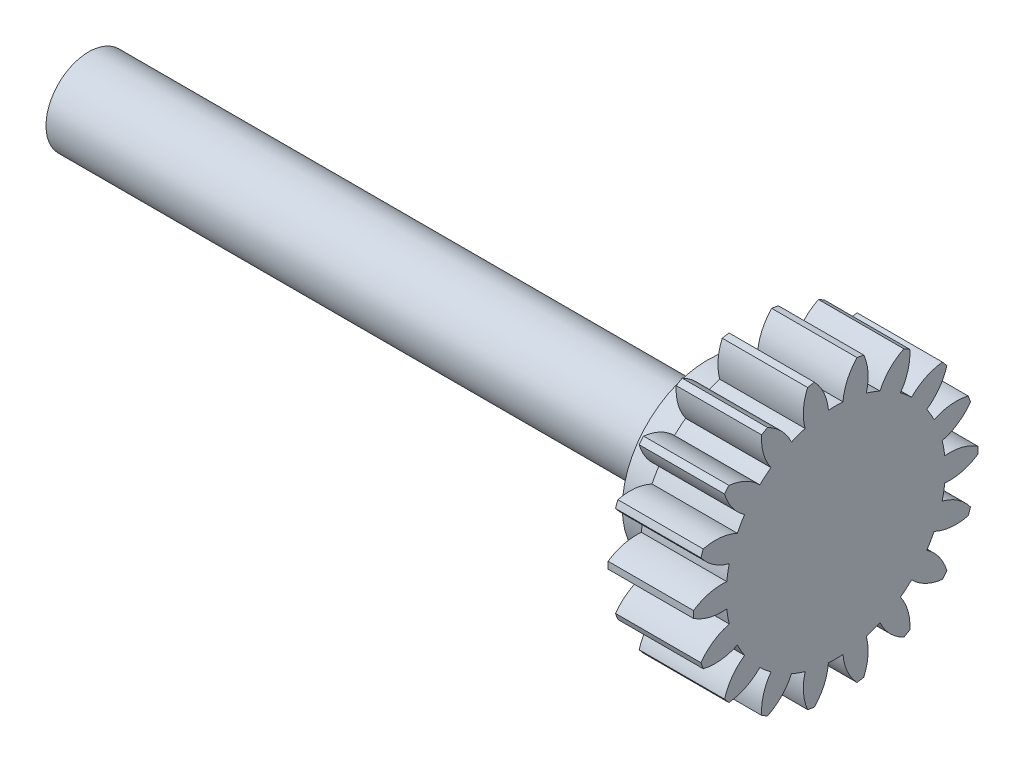
SolidWorks part; units mm, degrees
material "PET"
ref_plane "Plane1" through (0, 0, 0) normal (0, 0, 1) x (1, 0, 0)
ref_plane "Plane2" through (0, 0, 0) normal (0, 1, 0) x (1, 0, 0)
ref_plane "Plane3" through (0, 0, 0) normal (1, 0, 0) x (0, 0, -1)
sketch "HoldingSke" plane through (0, 0, 0) normal (0, 1, 0) x (1, 0, 0)
  line L0 (0, 0) -> (1159.5281, -376.7535)
  line L1 (-15, 0) -> (100, 0) construction
  line L2 (0, 0) -> (-2.1039, 2.3779)
  line L3 (0, 0) -> (-11.863, 4.5341)
  line L4 (0, 0) -> (8.2133, 2.6687)
  line L5 (0, 0) -> (-47.5972, -17.7524)
  line L6 (0, 0) -> (-2.632, -1.7758)
  line L7 (-2.1039, 2.3779) -> (8.8308, 51.9873)
  line L8 (-76.2, 54.61) -> (-75.184, 54.61)
  line L9 (-71.009, 38.7566) -> (-53.1078, 45.2721)
  line L10 (-76.2, 71.12) -> (104.1128, 71.12)
  line L11 (0, 0) -> (-3.175, 0)
  line L12 (-76.2, 101.6) -> (-76.1787, 101.6)
  line L13 (24.9733, 27.94) -> (52.9518, 28.4284)
  line L14 (24.9733, 27.94) -> (25.0241, 27.9398)
  line L15 (24.9733, 27.94) -> (100.4021, 29.52)
  circle A0 centre (0, 0) radius 0.3969
  circle A1 centre (0, 0) radius 4.0767
  circle A2 centre (0, 0) radius 38.1
  circle A3 centre (0, 0) radius 0.3969
  dimension "MHD" = 8.1534
  dimension "Hub_dia" = 76.2
  dimension "Bore" = 0.7937
  dimension "MBD" = 0.7937
  dimension "Num_teeth" = 18
  dimension "Pitch" = 1219.2
  dimension "Overall_len" = 50.8
  dimension "Show_teeth" = 18
  dimension "Thickness" = 3.175
  dimension "OAL" = 50.8002
  dimension "T_dim" = 1.016
  dimension "Ap" = 20
  dimension "H" = 19.05
  dimension "Pitch_radius" = 180.3128
  dimension "Width" = 3.175
  dimension "Backlash" = 0.0213
  dimension "Addendum_fac" = 1
  dimension "Dedendum_fac" = 1.2
  dimension "Clearance_fac" = 0.2
  dimension "Dedendum_add" = 0.0508
sketch "BasProSke" plane through (0, 0, 0) normal (0, 1, 0) x (1, 0, 0)
  line L0 (-10, 0) -> (60, 0) construction
  line L1 (0, 0) -> (0, 5.2917)
  line L2 (0, 0) -> (3.175, 0)
  line L3 (3.175, 0) -> (3.175, 5.2917)
  line L4 (3.175, 5.2917) -> (0, 5.2917)
  dimension "Thickness" = 3.175
  dimension "Diameter" = 10.5833
revolve "Base-Revolve" add sketch "BasProSke" angle 360 about L0
sketch "TooCutSke" plane through (0, 0, 0) normal (1, 0, 0) x (0, 0, -1)
  line L1 (0, 0) -> (0, 107) construction
  line L2 (0, 0) -> (-0.4524, 4.741) construction
  line L3 (0, 0) -> (-1.6488, 9.3507) construction
  line L4 (-0.4524, 4.741) -> (-0.8244, 4.6754) construction
  arc A0 (0.27, 4.0677) -> (-0.27, 4.0677) centre (0, 0) ccw
  arc A1 (0.8145, 5.2543) -> (-0.8145, 5.2543) centre (0, 0) ccw
  circle A2 centre (0, 0) radius 4.7625 construction
  circle A3 centre (0, 0) radius 4.4753 construction
  arc A4 (-0.27, 4.0677) -> (-0.8145, 5.2543) centre (-2.1688, 3.9146) ccw
  arc A5 (0.8145, 5.2543) -> (0.27, 4.0677) centre (2.1688, 3.9146) ccw
  dimension "Root_dia" = 8.1534
  dimension "Overcut_dia" = 10.6341
  dimension "Pitch_dia" = 9.525
  dimension "Base_dia" = 8.9506
  dimension "Flank_rad" = 1.905
  dimension "Half_ang" = 10
  dimension "Half_CT" = 0.3777
extrude "ToothCut" cut sketch "TooCutSke" along normal through all
fillet "Breaks" [suppressed] radius 0.0106 tangent propagation no
fillet "RootFillets" [suppressed] radius 0.1566
pattern_circular "TeethCuts" count 18 every 20 about axis through (-10, 0, 0) along (1, 0, 0) of "ToothCut", "RootFillets", "Breaks"
sketch "HubNeaOneSke" plane through (0, 0, 0) normal (-1, 0, 0) x (0, 0, 1)
  circle A0 centre (0, 0) radius 4.0767
  dimension "Diameter" = 8.1534
extrude "HubNearOne" [suppressed] add sketch "HubNeaOneSke" along normal blind 47.6252
sketch "HubNeaBotSke" plane through (0, 0, 0) normal (-1, 0, 0) x (0, 0, 1)
  circle A0 centre (0, 0) radius 4.0767
  dimension "Diameter" = 8.1534
extrude "HubNearBoth" [suppressed] add sketch "HubNeaBotSke" along normal blind 23.8126
ref_plane "FarPln" through (3.175, 0, 0) normal (1, 0, 0) x (0, 0, -1)
sketch "HubFarSke" plane through (3.175, 0, 0) normal (1, 0, 0) x (0, 0, -1)
  circle A0 centre (0, 0) radius 4.0767
  dimension "Diameter" = 8.1534
extrude "HubFar" [suppressed] add sketch "HubFarSke" along normal blind 23.8126
sketch "BorSke" plane through (0, 0, 0) normal (1, 0, 0) x (0, 0, -1)
  circle A0 centre (0, 0) radius 0.3969
  dimension "Diameter" = 0.7937
extrude "Bore" [suppressed] cut sketch "BorSke" along normal mid plane 101.6004
sketch "KeySke" plane through (0, 0, 0) normal (1, 0, 0) x (0, 0, -1)
  line L0 (-0.127, 0) -> (-0.127, 0.6191)
  line L1 (-0.127, 0.6191) -> (0.127, 0.6191)
  line L2 (0.127, 0.6191) -> (0.127, 0)
  line L3 (0, 0) -> (0, 34) construction
  line L4 (-0.127, 0) -> (0.127, 0)
  dimension "Offset" = 0.6191
  dimension "Width" = 0.254
extrude "Keyway" [suppressed] cut sketch "KeySke" along normal mid plane 101.6004
pattern_circular "Keyway2" [suppressed] count 2 every 90 about axis through (-10, 0, 0) along (1, 0, 0) reverse direction yes
sketch "Sketch1" [suppressed] plane through (0, 0, 0) normal (-1, 0, 0) x (0, 0, 1)
  circle A0 centre (0, 0) radius 2.7781
  dimension "D1" = 5.5562
extrude "Cut-Extrude2" [suppressed] cut sketch "Sketch1" against normal offset from surface (1.5875 mm away) 1.5875 up to face at (3.175, 0, 0)
sketch "Sketch2" plane through (0, 0, 0) normal (-1, 0, 0) x (0, 0, 1)
  circle A0 centre (0, 0) radius 1.5875
  dimension "D1" = 3.175
extrude "Cut-Extrude3" [suppressed] cut sketch "Sketch2" against normal through all contours A0
extrude "Boss-Extrude1" add sketch "Sketch2<3>" along normal blind 24.6062
sketch "Sketch2<3>" plane through (0, 0, 0) normal (-1, 0, 0) x (0, 0, 1) same geometry as "Sketch2"
sketch "Sketch3" plane through (0, 0, 0) normal (-1, 0, 0) x (0, 0, 1)
  circle A0 centre (0, 0) radius 3.175
  dimension "D1" = 6.35
extrude "Boss-Extrude2" add sketch "Sketch3" along normal blind 1.5875
ref_plane "Plane4" through (1.5875, 0, 0) normal (1, 0, 0) x (0, 0, -1)
sketch "Sketch4" plane through (1.5875, 0, 0) normal (1, 0, 0) x (0, 0, -1)
  circle A0 centre (0, 0) radius 4.7625
  dimension "D1" = 9.525
equation "' \"Pitch@HoldingSke\" = 4"
equation "'\"Num_teeth@HoldingSke\" = 18"
equation "' \"Ap@HoldingSke\" =  20"
equation "' \"Ap@HoldingSke\" = 20"
equation "' \"Width@HoldingSke\" = 0.5"
equation "' \"Hub_dia@HoldingSke\"= 1"
equation "' \"Hub_dia@HoldingSke\" = 1"
equation "' \"Overall_len@HoldingSke\" = 1.0"
equation "' \"Bore@HoldingSke\" = 0.75"
equation "' \"T_dim@HoldingSke\" = 0.85"
equation "' \"Width@KeySke\" = 0.25"
equation "' \"Show_teeth@HoldingSke\" = 13"
equation "' \"Backlash@HoldingSke\" = 0.009"
equation "' \"Addendum_fac@HoldingSke\" = 1.0"
equation "' \"Dedendum_fac@HoldingSke\" = 1.25"
equation "' \"Dedendum_add@HoldingSke\" = 0.00005"
equation "' \"Clearance_fac@HoldingSke\" = 0.25"
equation "' \"Pitch@HoldingSke\" = 0.5"
equation "' \"Num_teeth@HoldingSke\" = 23"
equation "' \"Show_teeth@HoldingSke\" = 23"
equation "' \"Backlash@HoldingSke\" = 0.0375"
equation "\"Overcut_dia@TooCutSke\" = (\"Num_teeth@HoldingSke\" + 2 * \"Addendum_fac@HoldingSke\") / \"Pitch@HoldingSke\" + 0.002"
equation "\"Pitch_dia@TooCutSke\" = \"Num_teeth@HoldingSke\" / \"Pitch@HoldingSke\""
equation "\"Base_dia@TooCutSke\" = \"Num_teeth@HoldingSke\" / \"Pitch@HoldingSke\" * cos((\"Ap@HoldingSke\"  * 3.14159265 / 180))"
equation "\"Root_dia@TooCutSke\" = (\"Num_teeth@HoldingSke\" + 2) / \"Pitch@HoldingSke\" - 2 * (\"Addendum_fac@HoldingSke\" + \"Dedendum_fac@HoldingSke\") / \"Pitch@HoldingSke\" - \"Dedendum_add@HoldingSke\" * 2"
equation "\"Half_ang@TooCutSke\" = 180 / \"Num_teeth@HoldingSke\""
equation "\"Half_CT@TooCutSke\" = \"Num_teeth@HoldingSke\" / \"Pitch@HoldingSke\" * sin((3.14159265 / 2 / \"Num_teeth@HoldingSke\")) / 2 - 7 * \"Backlash@HoldingSke\" / 4"
equation "\"Flank_rad@TooCutSke\" = \"Num_teeth@HoldingSke\" / \"Pitch@HoldingSke\" / 5"
equation "\"Radius@RootFillets\" = \"Clearance_fac@HoldingSke\" / \"Pitch@HoldingSke\" + \"Dedendum_add@HoldingSke\""
equation "\"Break_rad@Breaks\" = 0.02 / \"Pitch@HoldingSke\""
equation "\"Thickness@HoldingSke\" = \"Width@HoldingSke\""
equation "\"OAL@HoldingSke\" = \"Thickness@HoldingSke\""
equation "\"MHD@HoldingSke\" = (\"Num_teeth@HoldingSke\" + 2) / \"Pitch@HoldingSke\" - 2 * (\"Addendum_fac@HoldingSke\" + \"Dedendum_fac@HoldingSke\")  / \"Pitch@HoldingSke\" - \"Dedendum_add@HoldingSke\" * 2"
equation "\"MBD@HoldingSke\" = (\"Num_teeth@HoldingSke\" + 2) / \"Pitch@HoldingSke\" - 2 * (\"Addendum_fac@HoldingSke\" + \"Dedendum_fac@HoldingSke\")  / \"Pitch@HoldingSke\" - \"Dedendum_add@HoldingSke\" * 2 - 0.002"
equation "\"MHD@HoldingSke\" = ((sgn( \"MHD@HoldingSke\" - \"Hub_dia@HoldingSke\" )-1)*( \"MHD@HoldingSke\" - \"Hub_dia@HoldingSke\" ))/-2+ \"Hub_dia@HoldingSke\""
equation "\"MBD@HoldingSke\" = ((sgn( \"MBD@HoldingSke\" - \"Bore@HoldingSke\" )-1)*( \"MBD@HoldingSke\" - \"Bore@HoldingSke\" ))/-2+ \"Bore@HoldingSke\""
equation "\"OAL@HoldingSke\" = ((sgn( \"OAL@HoldingSke\" - \"Overall_len@HoldingSke\" )+1)*( \"OAL@HoldingSke\" - \"Overall_len@HoldingSke\" ))/2 + \"Overall_len@HoldingSke\" + 0.000002"
equation "\"Num_teeth@TeethCuts\" = int( \"Show_teeth@HoldingSke\" ) + 1"
equation "\"Num_teeth@TeethCuts\" = ((sgn( \"Num_teeth@TeethCuts\" - \"Num_teeth@HoldingSke\" )-1)*( \"Num_teeth@TeethCuts\" - \"Num_teeth@HoldingSke\" ))/-2+ \"Num_teeth@HoldingSke\""
equation "\"Num_teeth@TeethCuts\" = ((sgn( \"Num_teeth@TeethCuts\" - 2.0)+1)*( \"Num_teeth@TeethCuts\" - 2.0))/2 +2.0"
equation "\"Angle@TeethCuts\" = 360.0 / \"Num_teeth@HoldingSke\""
equation "\"Diameter@BasProSke\" = (\"Num_teeth@HoldingSke\" + 2 * \"Addendum_fac@HoldingSke\") / \"Pitch@HoldingSke\""
equation "\"Thickness@BasProSke\"  = \"Thickness@HoldingSke\""
equation "' \"Fillet_rad@BasProSke\" =  \"Thickness@HoldingSke\" * 0.05"
equation "' \"Fillet_rad@BasProSke\" = \"Thickness@HoldingSke\" * 0.05"
equation "\"MHD@HoldingSke\" = ((sgn( \"MHD@HoldingSke\" - \"Root_dia@TooCutSke\" )-1)*( \"MHD@HoldingSke\" - \"Root_dia@TooCutSke\" ))/-2+ \"Root_dia@TooCutSke\""
equation "\"Diameter@HubNeaOneSke\" = \"MHD@HoldingSke\""
equation "\"Length@HubNearOne\" = \"OAL@HoldingSke\" - \"Thickness@BasProSke\""
equation "\"Diameter@HubNeaBotSke\" = \"MHD@HoldingSke\""
equation "\"Length@HubNearBoth\" = ( \"OAL@HoldingSke\" - \"Thickness@BasProSke\" ) / 2.0"
equation "\"Thickness@FarPln\" = \"Thickness@BasProSke\""
equation "\"Diameter@HubFarSke\" = \"MHD@HoldingSke\""
equation "\"Length@HubFar\" = ( \"OAL@HoldingSke\" - \"Thickness@BasProSke\" ) / 2.0"
equation "\"Diameter@BorSke\" = \"MBD@HoldingSke\""
equation "\"D1@Bore\" = \"OAL@HoldingSke\" * 2.0"
equation "\"D1@Keyway\" = \"OAL@HoldingSke\" * 2.0"
equation "\"Offset@KeySke\" = \"T_dim@HoldingSke\" - \"MBD@HoldingSke\" / 2.0"
